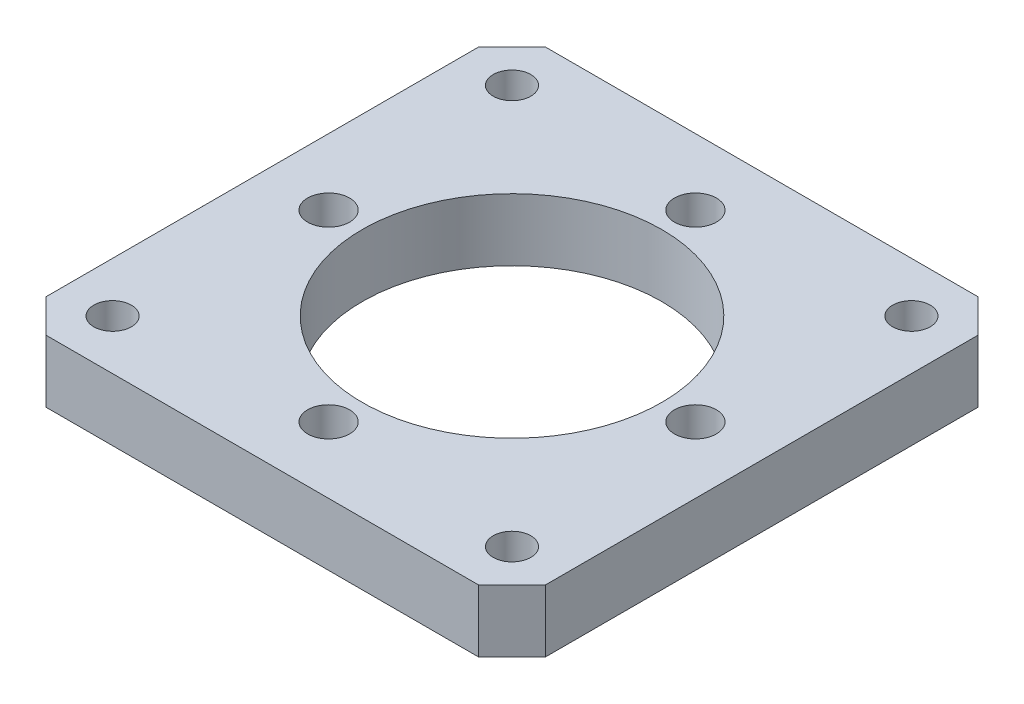
SolidWorks part; units mm, degrees
material "Alum Plate"
ref_plane "Front Plane" through (0, 0, 0) normal (0, 0, 1) x (1, 0, 0)
ref_plane "Top Plane" through (0, 0, 0) normal (0, 1, 0) x (1, 0, 0)
ref_plane "Right Plane" through (0, 0, 0) normal (1, 0, 0) x (0, 0, -1)
other "Bounding Box"
ref_plane "Default Plane" through (0, 2.286, 19.05) normal (0, -1, 0) x (-1, 0, 0)
sketch "Sketch1" plane through (0, 0, 0) normal (0, 1, 0) x (1, 0, 0)
  line L1 (-19.05, 19.05) -> (19.05, 19.05)
  line L2 (-19.05, 19.05) -> (-19.05, -19.05)
  line L3 (-19.05, -19.05) -> (19.05, -19.05)
  line L4 (19.05, 19.05) -> (19.05, -19.05)
  line L5 (-19.05, 19.05) -> (19.05, -19.05) construction
  line L6 (-19.05, -19.05) -> (19.05, 19.05) construction
  circle A0 centre (0, 0) radius 11.43
  point P0 (0, 0)
  dimension "D2" = 22.86
  dimension "D1" = 38.1
extrude "Boss-Extrude1" add sketch "Sketch1" along normal blind 4.7625
sketch "Sketch2" plane through (0, 4.7625, 0) normal (0, 1, 0) x (1, 0, 0)
  line L0 (0, 0) -> (0, 13.9954) construction
  line L1 (0, 0) -> (15.24, 15.24) construction
  line L2 (15.24, 15.24) -> (19.05, 15.24) construction
  line L3 (19.05, -19.05) -> (19.05, 19.05) construction
  line L4 (15.24, 15.24) -> (15.24, 19.05) construction
  line L5 (19.05, 19.05) -> (-19.05, 19.05) construction
  circle A0 centre (0, 13.9954) radius 1.6002
  circle A1 centre (15.24, 15.24) radius 1.4351
  dimension "D1" = 3.2004
  dimension "D3" = 2.8702
  dimension "D2" = 13.9954
  dimension "D4" = 3.81
extrude "Cut-Extrude1" cut sketch "Sketch2" against normal through all
pattern_circular "CirPattern1" count 4 over 360 about axis through (0, 4.7625, 0) along (0, -1, 0) of "Cut-Extrude1"
chamfer "Chamfer1" distance 2.54 angle 45 4 edges at (-19.05, 2.3813, 19.05) (19.05, 2.3813, 19.05) (19.05, 2.3813, -19.05) (-19.05, 2.3813, -19.05)
equation "\"Unit Measure\"= \"BoundingVolume\" / \"Thickness\"'in^2"
